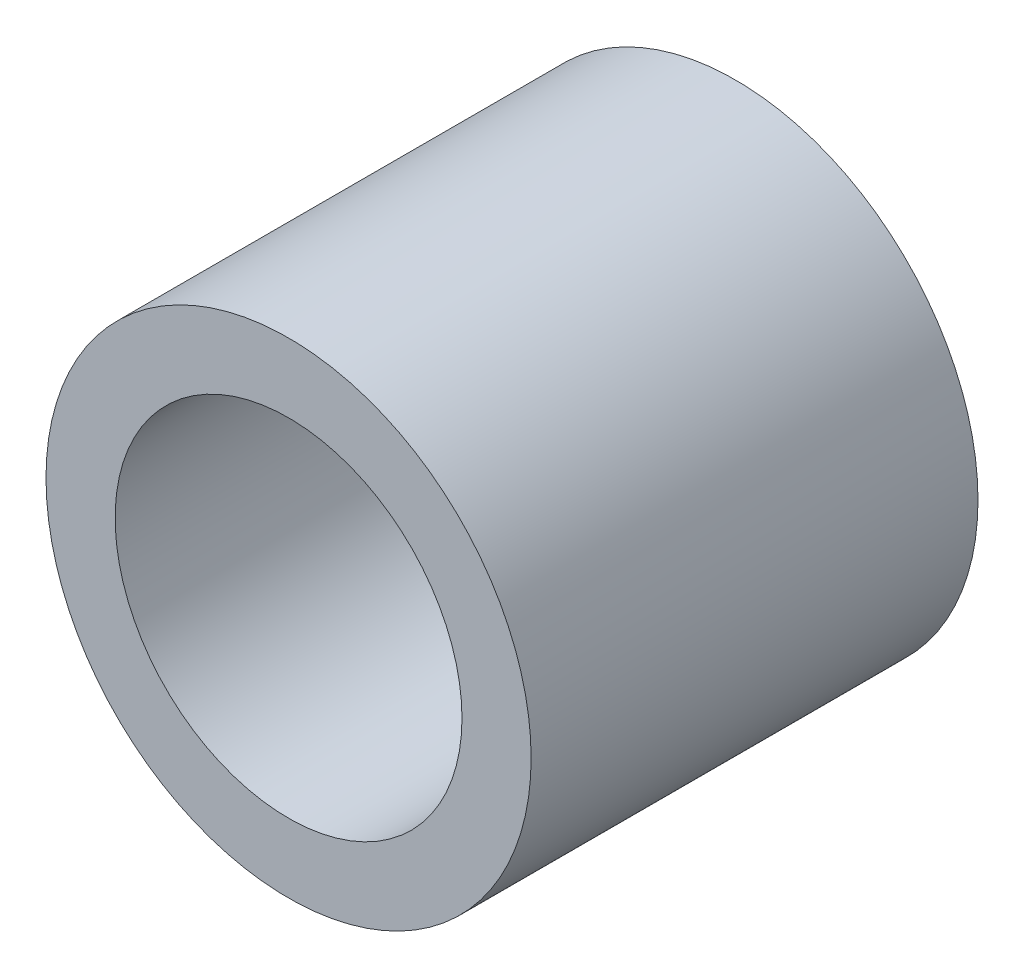
SolidWorks part; units mm, degrees
material "PET"
ref_plane "Front Plane" through (0, 0, 0) normal (0, 0, 1) x (1, 0, 0)
ref_plane "Top Plane" through (0, 0, 0) normal (0, 1, 0) x (1, 0, 0)
ref_plane "Right Plane" through (0, 0, 0) normal (1, 0, 0) x (0, 0, -1)
sketch "Sketch1" plane through (0, 0, 0) normal (0, 0, 1) x (1, 0, 0)
  circle A0 centre (0, 0) radius 3.9726
  circle A1 centre (0, 0) radius 5.5562
  dimension "D1" = 7.9451
  dimension "D2" = 11.1125
extrude "Boss-Extrude1" add sketch "Sketch1" along normal blind 10.2362
ref_axis "Axis1" through (0, 0, 10.2362) along (0, 0, -1)
